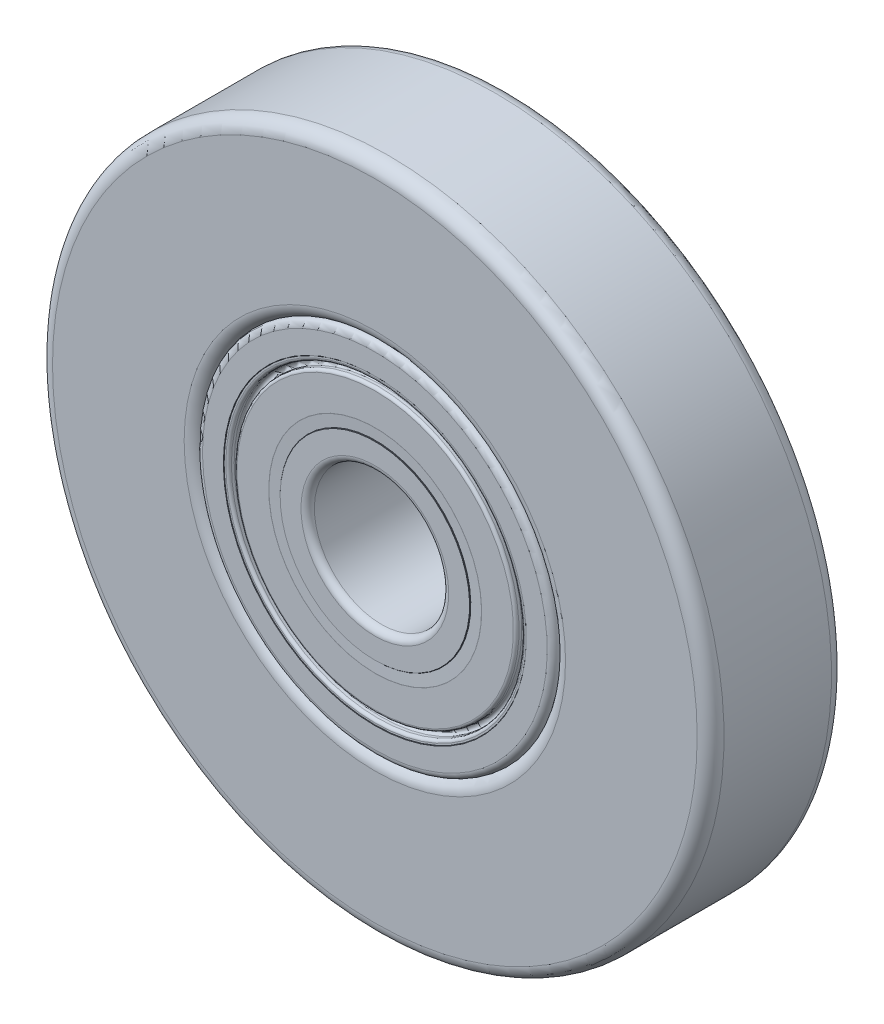
SolidWorks part; units mm, degrees
material "AISI 316 Annealed Stainless Steel Bar (SS)"
ref_plane "Front" through (0, 0, 0) normal (0, 0, 1) x (1, 0, 0)
ref_plane "Top" through (0, 0, 0) normal (0, 1, 0) x (1, 0, 0)
ref_plane "Right" through (0, 0, 0) normal (1, 0, 0) x (0, 0, -1)
sketch "LAYOUT R" plane through (0, 0, 0) normal (1, 0, 0) x (0, 0, -1)
  line L0 (-1.35, 1.5) -> (1.35, 1.5)
  line L1 (1.5, -4) -> (-1.5, -4) construction
  line L2 (1.5, -4) -> (1.5, 2.5781) construction
  line L3 (1.35, 4) -> (-1.35, 4)
  line L4 (-1.5, -4) -> (-1.5, 3.85) construction
  line L6 (2.6982, 0) -> (-2.6982, 0) construction
  line L7 (-1.492, 2.125) -> (1.492, 2.125)
  line L8 (-1.492, 3.375) -> (1.492, 3.375)
  line L11 (-8.89, 0) -> (8.89, 0) construction
  line L12 (-1.5, 3.85) -> (-1.5, 3.383)
  line L13 (1.5, 3.85) -> (1.5, 3.383)
  line L16 (-1.5, 2.117) -> (-1.5, 1.65)
  line L17 (1.5, 2.117) -> (1.5, 1.65)
  line L30 (-1.492, 3.375) -> (-1.492, 2.125) construction
  line L31 (1.492, 3.375) -> (1.492, 2.125) construction
  line L32 (-1.492, 2.375) -> (1.492, 2.375) construction
  line L33 (-1.4919, 2.375) -> (-1.481, 2.125)
  line L34 (1.4919, 2.375) -> (1.481, 2.125)
  line L35 (-1.492, 3.275) -> (1.492, 3.275) construction
  line L38 (-1.5, 3.383) -> (1.5, 3.383) construction
  line L39 (-1.492, 3.375) -> (-1.492, 3.3375)
  line L40 (-1.4295, 3.275) -> (-1.367, 3.275)
  line L41 (-1.492, 2.3777) -> (-1.492, 3.0875)
  line L42 (-1.4295, 3.15) -> (-1.367, 3.15)
  line L43 (1.492, 2.3777) -> (1.492, 3.0875)
  line L44 (1.4295, 3.15) -> (1.367, 3.15)
  line L45 (1.4295, 3.275) -> (1.367, 3.275)
  line L46 (-1.492, 3.15) -> (1.492, 3.15) construction
  line L50 (-1.3199, 3.125) -> (1.3199, 3.125) construction
  line L53 (1.492, 2.125) -> (1.5, 2.117)
  line L54 (-1.492, 2.125) -> (-1.5, 2.117)
  line L56 (-1.5, 2.117) -> (1.5, 2.117) construction
  line L57 (1.5, 3.383) -> (1.492, 3.375) construction
  line L58 (1.5, 3.383) -> (1.492, 3.375)
  line L60 (-1.5, 3.383) -> (-1.492, 3.375) construction
  line L61 (-1.5, 3.383) -> (-1.492, 3.375)
  line L64 (-1.367, 3.15) -> (-1.367, 3.275) construction
  line L65 (1.367, 3.15) -> (1.367, 3.275) construction
  line L66 (1.492, 3.375) -> (1.492, 3.3375)
  arc A2 (-1.4295, 3.15) -> (-1.492, 3.0875) centre (-1.4295, 3.0875) ccw
  arc A3 (1.492, 3.0875) -> (1.4295, 3.15) centre (1.4295, 3.0875) ccw
  arc A4 (1.4919, 2.375) -> (1.492, 2.3777) centre (1.4295, 2.3777) ccw
  arc A5 (-1.492, 2.3777) -> (-1.4919, 2.375) centre (-1.4295, 2.3777) ccw
  arc A6 (-1.367, 3.15) -> (-1.367, 3.275) centre (-1.367, 3.2125) ccw
  arc A7 (1.367, 3.275) -> (1.367, 3.15) centre (1.367, 3.2125) ccw
  arc A8 (-1.35, 4) -> (-1.5, 3.85) centre (-1.35, 3.85) ccw
  arc A9 (-1.5, 1.65) -> (-1.35, 1.5) centre (-1.35, 1.65) ccw
  arc A10 (1.35, 1.5) -> (1.5, 1.65) centre (1.35, 1.65) ccw
  arc A11 (-1.492, 3.3375) -> (-1.4295, 3.275) centre (-1.4295, 3.3375) ccw
  arc A12 (1.4295, 3.275) -> (1.492, 3.3375) centre (1.4295, 3.3375) ccw
  arc A13 (1.5, 3.85) -> (1.35, 4) centre (1.35, 3.85) ccw
  point P0 (0, 0)
  point P7 (-1.35, 4)
  point P8 (-1.4295, 3.275)
  point P15 (0, 0)
  point P29 (-1.492, 3.3375)
  point P38 (-1.4919, 2.375)
  point P54 (-1.492, 3.0875)
  point P55 (-1.4295, 3.15)
  point P56 (-1.492, 3.0875)
  point P58 (-1.492, 2.3777)
  point P59 (-1.4919, 2.375)
  point P60 (1.4295, 3.15)
  point P62 (1.492, 3.0875)
  point P63 (1.492, 2.3777)
  point P64 (1.4919, 2.375)
  point P71 (-1.5, 3.85)
  point P72 (-1.5, 1.65)
  point P73 (-1.35, 1.5)
  point P74 (1.35, 1.5)
  point P75 (1.5, 1.65)
  point P80 (1.35, 4)
  point P81 (1.4295, 3.275)
  point P88 (1.492, 3.3375)
  point P91 (1.5, 3.85)
  dimension "D21" = 0.125
  dimension "D33" = 0.15
  dimension "D3" = 1.5
  dimension "D4" = 2.125
  dimension "D5" = 3.375
  dimension "D24" = 3
  dimension "D6" = 2.992
  dimension "D7" = 2.992
  dimension "D11" = 0.25
  dimension "D12" = 2.5
  dimension "D13" = 2.5
  dimension "D14" = 0.1
  dimension "D17" = 0.008
  dimension "D18" = 0.125
  dimension "D19" = 0.125
  dimension "D20" = 0.125
  dimension "D15" = 0.25
  dimension "D23" = 45
  dimension "D25" = 45
  dimension "D27" = 0.008
  dimension "D28" = 4
  dimension "D29" = 3
  dimension "D30" = 8
  dimension "D8" = 1.5
  dimension "D31" = 45
  dimension "D32" = 45
sketch "Sketch R, INNER BODY" plane through (0, 0, 0) normal (1, 0, 0) x (0, 0, -1)
  line L1 (-1.492, 2.125) -> (-1.5, 2.117) construction
  line L3 (-1.5, 2.117) -> (-1.5, 1.65) construction
  line L12 (-8.89, 0) -> (8.89, 0) construction
  line L13 (-8.89, 0) -> (8.89, 0) construction
  line L14 (-1.35, 1.5) -> (1.35, 1.5) construction
  line L15 (1.5, 2.117) -> (1.5, 1.65) construction
  line L16 (1.492, 2.125) -> (1.5, 2.117) construction
  line L17 (-1.492, 2.125) -> (1.492, 2.125) construction
  line L18 (-1.492, 2.125) -> (-1.5, 2.117)
  line L19 (-1.5, 2.117) -> (-1.5, 1.65)
  line L20 (-1.35, 1.5) -> (1.35, 1.5)
  line L21 (1.5, 2.117) -> (1.5, 1.65)
  line L22 (1.492, 2.125) -> (1.5, 2.117)
  line L23 (-1.492, 2.125) -> (1.492, 2.125)
  arc A0 (-1.5, 1.65) -> (-1.35, 1.5) centre (-1.35, 1.65) ccw construction
  arc A1 (1.35, 1.5) -> (1.5, 1.65) centre (1.35, 1.65) ccw construction
  arc A2 (-1.5, 1.65) -> (-1.35, 1.5) centre (-1.35, 1.65) ccw
  arc A3 (1.35, 1.5) -> (1.5, 1.65) centre (1.35, 1.65) ccw
sketch "Sketch R, OUTER BODY" plane through (0, 0, 0) normal (1, 0, 0) x (0, 0, -1)
  line L8 (-8.89, 0) -> (8.89, 0) construction
  line L9 (-8.89, 0) -> (8.89, 0) construction
  line L31 (-1.5, 3.85) -> (-1.5, 3.383) construction
  line L84 (-1.5, 3.383) -> (-1.492, 3.375) construction
  line L85 (-1.492, 3.375) -> (1.492, 3.375) construction
  line L86 (1.5, 3.383) -> (1.492, 3.375) construction
  line L87 (1.5, 3.85) -> (1.5, 3.383) construction
  line L88 (1.35, 4) -> (-1.35, 4) construction
  line L89 (-1.5, 3.85) -> (-1.5, 3.383)
  line L90 (-1.5, 3.383) -> (-1.492, 3.375)
  line L91 (-1.492, 3.375) -> (1.492, 3.375)
  line L92 (1.5, 3.383) -> (1.492, 3.375)
  line L93 (1.5, 3.85) -> (1.5, 3.383)
  line L94 (1.35, 4) -> (-1.35, 4)
  arc A6 (1.5, 3.85) -> (1.35, 4) centre (1.35, 3.85) ccw construction
  arc A7 (-1.35, 4) -> (-1.5, 3.85) centre (-1.35, 3.85) ccw construction
  arc A8 (1.5, 3.85) -> (1.35, 4) centre (1.35, 3.85) ccw
  arc A9 (-1.35, 4) -> (-1.5, 3.85) centre (-1.35, 3.85) ccw
sketch "Sketch R, SHIELD FACES" plane through (0, 0, 0) normal (1, 0, 0) x (0, 0, -1)
  line L0 (-8.89, 0) -> (8.89, 0) construction
  line L1 (-8.89, 0) -> (8.89, 0) construction
  line L29 (-1.492, 3.375) -> (-1.492, 3.3375) construction
  line L32 (-1.4295, 3.275) -> (-1.367, 3.275) construction
  line L34 (-1.4295, 3.15) -> (-1.367, 3.15) construction
  line L36 (-1.492, 2.3777) -> (-1.492, 3.0875) construction
  line L38 (-1.4919, 2.375) -> (-1.481, 2.125) construction
  line L39 (-1.492, 2.125) -> (1.492, 2.125) construction
  line L40 (1.4919, 2.375) -> (1.481, 2.125) construction
  line L43 (1.492, 2.3777) -> (1.492, 3.0875) construction
  line L79 (1.4295, 3.15) -> (1.367, 3.15) construction
  line L80 (1.4295, 3.275) -> (1.367, 3.275) construction
  line L81 (1.492, 3.375) -> (1.492, 3.3375) construction
  line L82 (-1.492, 3.375) -> (1.492, 3.375) construction
  line L83 (-1.492, 3.375) -> (-1.492, 3.3375)
  line L84 (-1.4295, 3.275) -> (-1.367, 3.275)
  line L85 (-1.4295, 3.15) -> (-1.367, 3.15)
  line L86 (-1.492, 2.3777) -> (-1.492, 3.0875)
  line L87 (-1.4919, 2.375) -> (-1.481, 2.125)
  line L88 (-1.481, 2.125) -> (1.481, 2.125)
  line L89 (1.4919, 2.375) -> (1.481, 2.125)
  line L90 (1.492, 2.3777) -> (1.492, 3.0875)
  line L91 (1.4295, 3.15) -> (1.367, 3.15)
  line L92 (1.4295, 3.275) -> (1.367, 3.275)
  line L93 (1.492, 3.375) -> (1.492, 3.3375)
  line L94 (-1.492, 3.375) -> (1.492, 3.375)
  arc A28 (-1.492, 3.3375) -> (-1.4295, 3.275) centre (-1.4295, 3.3375) ccw construction
  arc A29 (-1.367, 3.15) -> (-1.367, 3.275) centre (-1.367, 3.2125) ccw construction
  arc A30 (-1.4295, 3.15) -> (-1.492, 3.0875) centre (-1.4295, 3.0875) ccw construction
  arc A31 (1.492, 3.0875) -> (1.4295, 3.15) centre (1.4295, 3.0875) ccw construction
  arc A32 (1.367, 3.275) -> (1.367, 3.15) centre (1.367, 3.2125) ccw construction
  arc A33 (1.4295, 3.275) -> (1.492, 3.3375) centre (1.4295, 3.3375) ccw construction
  arc A34 (-1.492, 3.3375) -> (-1.4295, 3.275) centre (-1.4295, 3.3375) ccw
  arc A35 (-1.367, 3.15) -> (-1.367, 3.275) centre (-1.367, 3.2125) ccw
  arc A36 (-1.4295, 3.15) -> (-1.492, 3.0875) centre (-1.4295, 3.0875) ccw
  arc A37 (1.492, 3.0875) -> (1.4295, 3.15) centre (1.4295, 3.0875) ccw
  arc A38 (1.367, 3.275) -> (1.367, 3.15) centre (1.367, 3.2125) ccw
  arc A39 (1.4295, 3.275) -> (1.492, 3.3375) centre (1.4295, 3.3375) ccw
  arc A40 (-1.492, 2.3777) -> (-1.4919, 2.375) centre (-1.4295, 2.3777) ccw construction
  arc A41 (-1.492, 2.3777) -> (-1.4919, 2.375) centre (-1.4295, 2.3777) ccw
  arc A42 (1.4919, 2.375) -> (1.492, 2.3777) centre (1.4295, 2.3777) ccw construction
  arc A43 (1.4919, 2.375) -> (1.492, 2.3777) centre (1.4295, 2.3777) ccw
revolve "Revolve INNER BODY" add sketch "Sketch R, INNER BODY" angle 360 about L13
revolve "Revolve OUTER BODY" add sketch "Sketch R, OUTER BODY" angle 360 about L9
revolve "Revolve SHIELDS" add sketch "Sketch R, SHIELD FACES" angle 360 about L1
sketch "草图1" plane through (0, 0, 0) normal (0, 0, 1) x (1, 0, 0)
  circle A0 centre (0, 0) radius 4 construction
  circle A1 centre (0, 0) radius 4
  circle A2 centre (0, 0) radius 7.5
  dimension "D1" = 15
extrude "凸台-拉伸2" add sketch "草图1" along normal blind 3 from surface starting at face at (0, -3.85, -1.5)
fillet "圆角1" radius 0.3 3 edges at (0, -7.5, -1.5) (0, -4, 1.5) (0, -7.5, 1.5)
equation "\"_i__BORE\"= 3"
equation "\"_i__OUTSIDE_DIAMETER\"= 8"
equation "\"_i__WIDTH\"= 3"
equation "\"_user_applied_FONT_SIZ\"= 0"
equation "\"BODY__HALF_WIDTH\"= \"_i__WIDTH\" / 2"
equation "\"BODY_SPAN___OF_DIAMETER\"= \"_i__OUTSIDE_DIAMETER\" - \"_i__BORE\""
equation "\"BODY_SPAN___OF_RADIUS\"= \"BODY_SPAN___OF_DIAMETER\" / 2"
equation "\"BODY_SPAN__BORE_AND_OD__OF RADIUS\"= ( \"BODY_SPAN___OF_RADIUS\" - \"BODY_SPAN__SHIELD__OF_RADIUS\" ) / 2"
equation "\"BODY_SPAN__SHIELD__OF_RADIUS\"= \"BODY_SPAN___OF_RADIUS\" * \"g_param__SHIELD_PANEL_SPAN__RATIO_OF_BODY_RADIAN\""
equation "\"BORE__RADIUS\"= \"_i__BORE\" / 2"
equation "\"CORNER_RADII\"= \"_i__WIDTH\" * \"g_param__CORNER_RADII__RATIO_TO_WIDTH\""
equation "\"OUTSIDE_RADIUS\"= \"_i__OUTSIDE_DIAMETER\" / 2"
equation "\"RING_INNER__OUTSIDE_RADIUS\"= \"BORE__RADIUS\" + \"BODY_SPAN__BORE_AND_OD__OF RADIUS\""
equation "\"RING_OUTER__INSIDE_DIAMETER\"= \"RING_OUTER__INSIDE_RADIUS\" * 2"
equation "\"RING_OUTER__INSIDE_RADIUS\"= ( \"_i__OUTSIDE_DIAMETER\" / 2 ) - \"BODY_SPAN__BORE_AND_OD__OF RADIUS\""
equation "\"SHIELD__BOTTOM_AND_TOP_REGIONS_SPAN\"= \"BODY_SPAN__SHIELD__OF_RADIUS\" * \"g_param__SHIELD__TOP_AND_BOTTOM_REGIONS_RATIO\""
equation "\"SHIELD__COMPRESSION_FILLET_DIAMETER\"= \"BODY_SPAN__SHIELD__OF_RADIUS\" * \"g_param__SHIELD_COMPRESSION_FILLET_DIAMETER_RATIO\""
equation "\"SHIELD__COMPRESSION_FILLET_RADIUS\"= \"SHIELD__COMPRESSION_FILLET_DIAMETER\" / 2"
equation "\"SHIELD__FACE_FILLET_DIAMETER\"= \"BODY_SPAN__SHIELD__OF_RADIUS\" * \"g_param__SHIELD_FACE_FILLET_RATIO\""
equation "\"SHIELD__FACE_INSET\"= \"SIDE_FACE_CHAMFERS\""
equation "\"SHIELD__FACE_TO_OPPOSING_BRG_BODY_FACE\"= \"_i__WIDTH\" - \"SHIELD__FACE_INSET\""
equation "\"SHIELD__HALF_SLIT_WIDTH\"= \"SHIELD__SLIT_WIDTH\" / 2"
equation "\"SHIELD__HALF_WALL\"= \"SHIELD__WALL\" / 2"
equation "\"SHIELD__SLIT_WIDTH\"= \"SHIELD__WALL\" / 5"
equation "\"SHIELD__WALL\"= \"BODY_SPAN__SHIELD__OF_RADIUS\" * \"g_param__SHIELD_WALL_TO_SPAN_RATIO\""
equation "\"SHIELD_SLIT__INSIDE_TERMINUS__DIAMETER\"= \"RING_OUTER__INSIDE_DIAMETER\" - \"SHIELD__BOTTOM_AND_TOP_REGIONS_SPAN\""
equation "\"SHIELD_SLIT__KEYHOLE_DIAMETER\"= \"SHIELD__SLIT_WIDTH\" * 1.5"
equation "\"SIDE_FACE_CHAMFERS\"= \"_i__OUTSIDE_DIAMETER\" * \"g_param__SIDE_CHAMFERS__RATIO_TO_OD\""
equation "\"TEXT_RADIUS\"= \"_i__BORE\" + ( \"BODY_SPAN___OF_DIAMETER\" / 2 ) - \"_user_applied_FONT_SIZ\""
equation "\"WIDTH__HALF\"= \"_i__WIDTH\" / 2"
equation "\"D11@LAYOUT R\"= \"SHIELD__BOTTOM_AND_TOP_REGIONS_SPAN\""
equation "\"D12@LAYOUT R\" = \"g_param__SHIELD__INSIDE_BEVEL_ANGLE__DEGREES\""
equation "\"D13@LAYOUT R\"= \"g_param__SHIELD__INSIDE_BEVEL_ANGLE__DEGREES\""
equation "\"D14@LAYOUT R\"=\"SHIELD__WALL\""
equation "\"D15@LAYOUT R\"=\"SHIELD__BOTTOM_AND_TOP_REGIONS_SPAN\""
equation "\"D17@LAYOUT R\"=\"SIDE_FACE_CHAMFERS\""
equation "\"D18@LAYOUT R\"=\"SHIELD__COMPRESSION_FILLET_DIAMETER\""
equation "\"D19@LAYOUT R\"=\"SHIELD__COMPRESSION_FILLET_DIAMETER\""
equation "\"D20@LAYOUT R\"=\"SHIELD__COMPRESSION_FILLET_DIAMETER\""
equation "\"D21@LAYOUT R\"=\"SHIELD__FACE_FILLET_DIAMETER\""
equation "\"D24@LAYOUT R\"=\"_i__WIDTH\""
equation "\"D27@LAYOUT R\"=\"SIDE_FACE_CHAMFERS\""
equation "\"D28@LAYOUT R\"=\"OUTSIDE_RADIUS\""
equation "\"D3@LAYOUT R\"=\"BORE__RADIUS\""
equation "\"D30@LAYOUT R\"=\"_i__OUTSIDE_DIAMETER\""
equation "\"D33@LAYOUT R\"=\"CORNER_RADII\""
equation "\"D4@LAYOUT R\"=\"RING_INNER__OUTSIDE_RADIUS\""
equation "\"D5@LAYOUT R\"=\"RING_OUTER__INSIDE_RADIUS\""
equation "\"D6@LAYOUT R\"=\"SHIELD__FACE_TO_OPPOSING_BRG_BODY_FACE\""
equation "\"D7@LAYOUT R\"=\"SHIELD__FACE_TO_OPPOSING_BRG_BODY_FACE\""
equation "\"D8@LAYOUT R\"=\"WIDTH__HALF\""
equation "\"g_param__CORNER_RADII__RATIO_TO_WIDTH\"= 0.05'ISO MAX IS 0.07 WHERE WIDTH IS LESS THAN DIAMETER"
equation "\"g_param__FONT_SIZE_RATIO\"= 0.15'EXPRESSES RADIAL PROPORTION OF SHIELD FACE"
equation "\"g_param__INDICIA__EXTRUSION_DEPTH\"=0.013'CONCAVE-EMBOSSED INDICIA ON SHIELD FACES"
equation "\"g_param__SHIELD__INSIDE_BEVEL_ANGLE__DEGREES\"= 2.5'SHOULD BE GREATER THAN 0 AND LESS THAN OR EQUAL TO 10, ORIGINALLY 1"
equation "\"g_param__SHIELD__NUMBER_OF_SLITS\"=26'OPTIONAL NUMBER OF SHIELD COMPRESSION RING SLITS"
equation "\"g_param__SHIELD__TOP_AND_BOTTOM_REGIONS_RATIO\"=0.2'PART OF RADIAL SHIELD SPAN OCCUPIED BY INMOST BEVEL, ORIGINALLY 0.2"
equation "\"g_param__SHIELD_COMPRESSION_FILLET_DIAMETER_RATIO\"=0.1'ORIGINALLY 0,1"
equation "\"g_param__SHIELD_FACE_FILLET_RATIO\"=0.1'ORIGINALLY 0.1"
equation "\"g_param__SHIELD_FACE_INSET__RATIO_OF_WIDTH\"= 0.035'ISO-UNSPECIFIED, SHOULD BE AT LEAST 0.025 and LESS THAN 0.036"
equation "\"g_param__SHIELD_PANEL_SPAN__RATIO_OF_BODY_RADIAN\"= 0.5'ISO-UNSPECIFIED, ORIGINALLY 0.5"
equation "\"g_param__SHIELD_WALL_TO_SPAN_RATIO\"=0.08'SHOULD BE LESS THAN 0.015, ORIGINALLY 0.08, PRESCRIBES MATERIAL THICKNESS"
equation "\"g_param__SIDE_CHAMFERS__RATIO_TO_OD\"= 0.001'NOT ISO-SPECIFIED"
